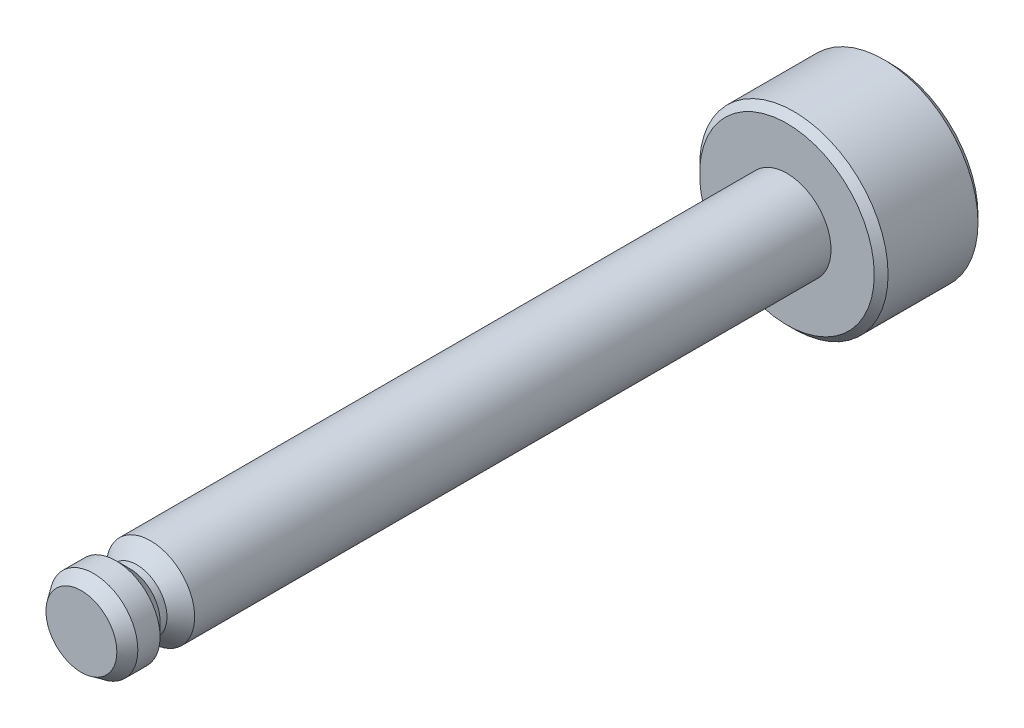
SolidWorks part; units mm, degrees
ref_plane "Front" through (0, 0, 0) normal (0, 0, 1) x (1, 0, 0)
ref_plane "Top" through (0, 0, 0) normal (0, 1, 0) x (1, 0, 0)
ref_plane "Right" through (0, 0, 0) normal (1, 0, 0) x (0, 0, -1)
sketch "Sketch2" plane through (0, 0, 0) normal (0, 0, 1) x (1, 0, 0)
  circle A0 centre (0, 0) radius 1.275
  dimension "D1" = 2.55
extrude "Shaft" add sketch "Sketch2" along normal blind 20.4
sketch "Sketch5" plane through (0, 0, 0) normal (0, 0, 1) x (1, 0, 0)
  circle A0 centre (0, 0) radius 2.725
  dimension "D1" = 5.45
extrude "Head" add sketch "Sketch5" against normal blind 3
chamfer "Chamfer1" distance 0.25 angle 55 1 edges at (1.275, 0, 20.4) first distance on face at (1.275, 0, 20.4)
chamfer "Deburs" distance 0.2 angle 45 2 edges at (2.725, 0, 0) (2.725, 0, -3)
sketch "Sketch6" plane through (0, 0, 0) normal (1, 0, 0) x (0, 0, -1)
  line L0 (0, 0) -> (-18.9, 0) construction
  line L1 (-18.9, 0) -> (-18.9, 0.875) construction
  line L2 (0, 1.275) -> (-20.043, 1.275) construction
  line L3 (-19.4, 1.275) -> (-18.4, 1.275)
  line L4 (-18.4, 1.275) -> (-18.8, 0.875)
  line L5 (-18.8, 0.875) -> (-19, 0.875)
  line L6 (-19, 0.875) -> (-19.4, 1.275)
  line L7 (-18.9, 0.875) -> (-18.9, 1.275) construction
  dimension "D1" = 18.9
  dimension "D2" = 0.4
  dimension "D3" = 1
revolve "e-Clip Notch Long" cut sketch "Sketch6" angle 360 about L0
equation "\"D1@Sketch2\"=\"Plastic Hardware OD@Box Assy.Assembly\""
equation "\"D1\"= \"Countersink Diameter@Box Assy.Assembly\" - .3mm"
equation "\"D1@Head\"=\"Countersink Depth@Box Assy.Assembly\""
equation "\"Length\"= 20mm"
equation "\"D1@Shaft\"=\"Length\"+.4mm"
equation "\"D1@Sketch6\"=\"Length\"-1.1mm"
